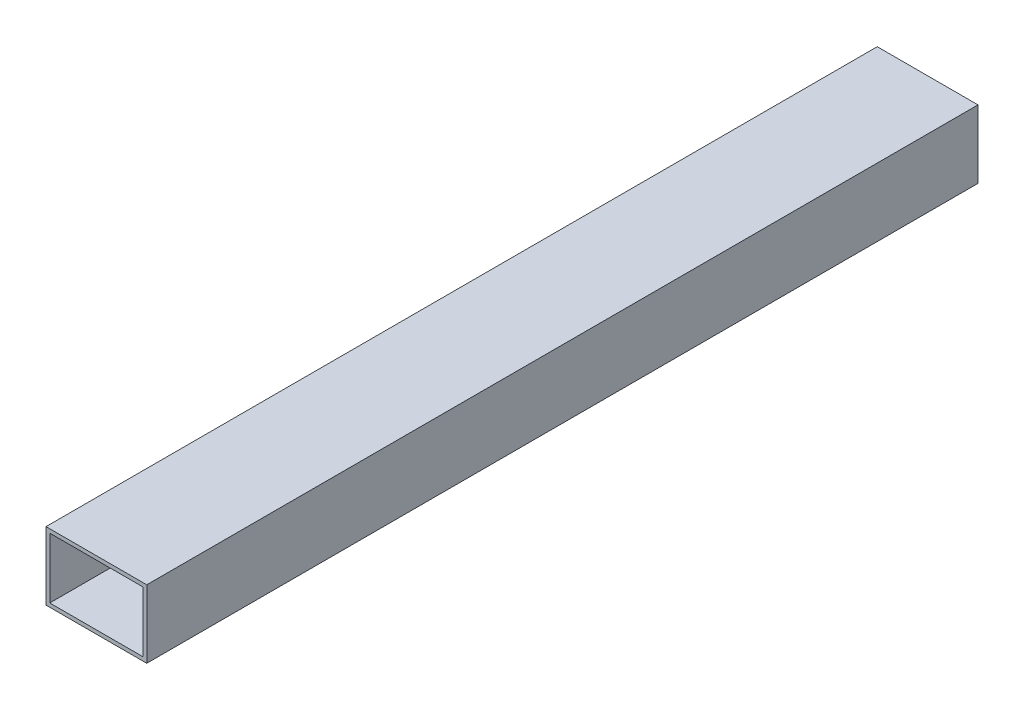
SolidWorks part; units mm, degrees
material "AISI 1020 Acier laminé à froid"
ref_plane "Plan de face" through (0, 0, 0) normal (0, 0, 1) x (1, 0, 0)
ref_plane "Plan de dessus" through (0, 0, 0) normal (0, 1, 0) x (1, 0, 0)
ref_plane "Plan de droite" through (0, 0, 0) normal (1, 0, 0) x (0, 0, -1)
sketch "Esquisse1" plane through (0, 0, 0) normal (0, 0, 1) x (1, 0, 0)
  line L1 (0, 0) -> (40, 0)
  line L2 (0, 0) -> (0, 27)
  line L3 (0, 27) -> (40, 27)
  line L4 (40, 0) -> (40, 27)
  line L5 (1.5, 25.5) -> (38.5, 25.5)
  line L6 (1.5, 25.5) -> (1.5, 1.5)
  line L7 (1.5, 1.5) -> (38.5, 1.5)
  line L8 (38.5, 25.5) -> (38.5, 1.5)
  dimension "D1" = 40
  dimension "D2" = 27
  dimension "D3" = 1.5
  dimension "D4" = 1.5
  dimension "D5" = 1.5
  dimension "D6" = 1.5
extrude "Boss.-Extru.1" add sketch "Esquisse1" along normal blind 330
